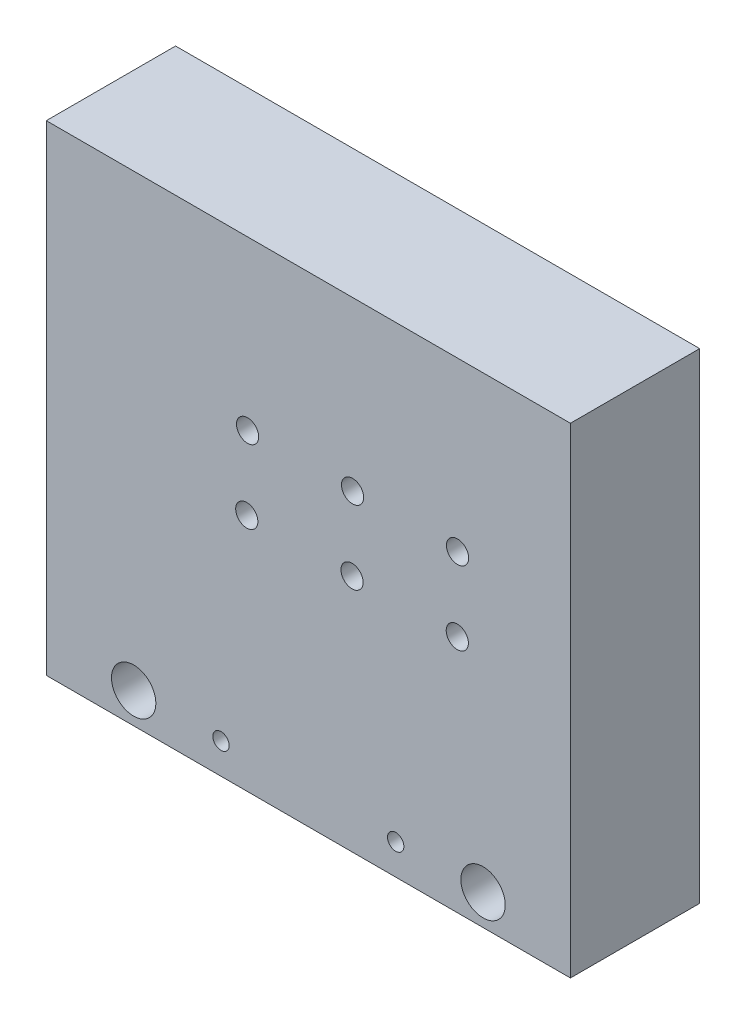
SolidWorks part; units mm, degrees
material "6061-T6 (SS)"
ref_plane "Ground Plane" through (0, 0, 0) normal (0, 0, 1) x (1, 0, 0)
ref_plane "Center Plane" through (0, 0, 0) normal (0, 1, 0) x (1, 0, 0)
ref_plane "Left Plane" through (0, 0, 0) normal (1, 0, 0) x (0, 0, -1)
ref_axis "FRONT (X)" through (88.99, 0, 0) along (-1, 0, 0)
ref_axis "LEFT (Y)" through (0, 55, 0) along (0, -1, 0)
ref_axis "UP (Z)" through (0, 0, 55) along (0, 0, -1)
sketch "Sketch1" plane through (0, 0, 0) normal (0, 0, 1) x (1, 0, 0)
  line L8 (0, 275) -> (0, 0)
  line L10 (300, 275) -> (300, 0)
  line L11 (300, 0) -> (0, 0)
  line L12 (235.4036, 178.9997) -> (235.25, 136.75) construction
  line L13 (300, 275) -> (0, 275)
  line L14 (175.3073, 178.9989) -> (175, 136.75) construction
  line L15 (115.2109, 178.9975) -> (114.75, 136.75) construction
  circle A22 centre (250, 17.5) radius 12.7
  circle A23 centre (200, 17.5) radius 4.675
  circle A25 centre (100, 17.5) radius 4.675
  circle A26 centre (50, 17.5) radius 12.7
  circle A29 centre (235.25, 136.75) radius 3
  circle A31 centre (114.75, 136.75) radius 3
  circle A32 centre (175, 136.75) radius 3
  circle A33 centre (115.2109, 178.9975) radius 3
  circle A34 centre (175.3073, 178.9989) radius 3
  circle A35 centre (235.4036, 178.9997) radius 3
  dimension "D1" = 300
  dimension "D3" = 6
  dimension "D4" = 6
  dimension "D5" = 9.35
  dimension "D6" = 9.35
  dimension "D7" = 25.4
  dimension "D8" = 25.4
  dimension "D9" = 6
  dimension "D10" = 6
  dimension "D11" = 6
  dimension "D12" = 6
  dimension "D2" = 275
extrude "Boss-Extrude1" add sketch "Sketch1" along normal blind 74
sketch "Sketch2" plane through (0, 0, 74) normal (0, 0, -1) x (-1, 0, 0)
  circle A0 centre (-175, 136.75) radius 6.35
  circle A1 centre (-235.25, 136.75) radius 6.35
  circle A2 centre (-235.4036, 178.9997) radius 6.35
  circle A3 centre (-175.3073, 178.9989) radius 6.35
  circle A4 centre (-115.2109, 178.9975) radius 6.35
  circle A5 centre (-114.75, 136.75) radius 6.35
  dimension "D1" = 12.7
  dimension "D2" = 12.7
  dimension "D3" = 12.7
  dimension "D4" = 12.7
  dimension "D5" = 12.7
  dimension "D6" = 12.7
extrude "Cut-Extrude1" cut sketch "Sketch2" along normal blind 45
